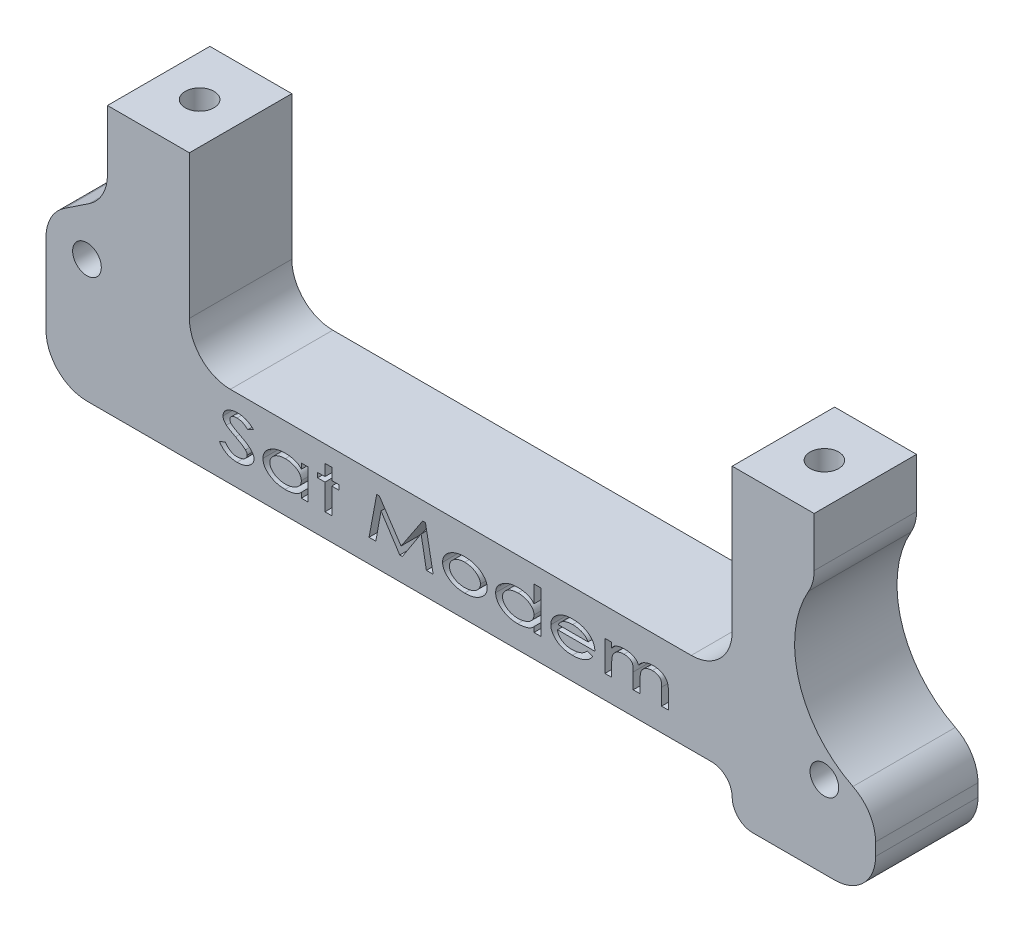
SolidWorks part; units mm, degrees
ref_plane "Front Plane" through (0, 0, 0) normal (0, 0, 1) x (1, 0, 0)
ref_plane "Top Plane" through (0, 0, 0) normal (0, 1, 0) x (1, 0, 0)
ref_plane "Right Plane" through (0, 0, 0) normal (1, 0, 0) x (0, 0, -1)
sketch "Sketch1" plane through (0, 0, 0) normal (0, 0, 1) x (1, 0, 0)
  line L0 (0, 0) -> (-2.54, 0)
  line L1 (0, 0) -> (2.54, 0)
  line L2 (-2.54, 0) -> (-2.54, 6.35)
  line L3 (0, 0) -> (0, 5.08) construction
  line L4 (0, 5.08) -> (0, 13.97) construction
  line L5 (0, 13.97) -> (3.81, 13.97) construction
  line L6 (3.81, 13.97) -> (6.35, 13.97)
  line L7 (3.81, 13.97) -> (1.27, 13.97)
  line L8 (1.27, 13.97) -> (1.27, 8.89)
  line L10 (6.35, 13.97) -> (6.35, 8.89)
  line L11 (2.54, 0) -> (2.54, 6.35)
  line L13 (2.54, 6.35) -> (6.35, 8.89)
  line L14 (-2.54, 6.35) -> (1.27, 8.89)
  circle A0 centre (0, 5.08) radius 0.889
extrude "Boss-Extrude1" add sketch "Sketch1" along normal blind 6.35
ref_plane "Plane1" through (0, 13.97, 0) normal (0, 1, 0) x (1, 0, 0)
sketch "Sketch2" plane through (0, 13.97, 0) normal (0, 1, 0) x (1, 0, 0)
  line L0 (3.81, -6.35) -> (3.81, -3.175) construction
  line L1 (6.35, -6.35) -> (1.27, -6.35) construction
  circle A0 centre (3.81, -3.175) radius 0.889
extrude "Cut-Extrude1" cut sketch "Sketch2" against normal blind 5.08
ref_plane "Plane2" through (0, 0, 6.35) normal (0, 0, 1) x (1, 0, 0)
sketch "Sketch3" plane through (0, 0, 6.35) normal (0, 0, 1) x (1, 0, 0)
  line L1 (2.54, 0) -> (2.54, 6.35) construction
  line L2 (3.81, 13.97) -> (3.81, 5.08) construction
  line L3 (6.35, 13.97) -> (1.27, 13.97) construction
  line L4 (3.81, 5.08) -> (42.545, 5.08) construction
  line L5 (42.545, 5.08) -> (42.545, 13.97) construction
  line L6 (42.545, 13.97) -> (40.005, 13.97)
  line L7 (42.545, 13.97) -> (45.085, 13.97)
  line L8 (45.085, 13.97) -> (45.085, 10.16)
  line L11 (45.085, 10.16) -> (45.085, 6.35) construction
  line L12 (48.895, -5.08) -> (48.895, 0)
  line L13 (42.545, -5.08) -> (45.72, -5.08) construction
  line L14 (45.72, -5.08) -> (45.72, 0) construction
  line L15 (40.005, -5.08) -> (48.895, -5.08)
  line L19 (40.005, 5.08) -> (40.005, 13.97)
  line L20 (2.54, 0) -> (2.54, 5.08)
  line L22 (6.35, 8.89) -> (6.35, 5.08)
  line L23 (2.54, 5.08) -> (2.54, 6.35)
  line L24 (2.54, 6.35) -> (6.35, 8.89)
  line L26 (6.35, 5.08) -> (6.35, 2.54)
  line L27 (6.35, 2.54) -> (6.35, -2.54) construction
  line L28 (6.35, -2.54) -> (-2.54, -2.54)
  line L29 (-2.54, -2.54) -> (-2.54, 0)
  line L30 (-2.54, 0) -> (2.54, 0)
  line L31 (6.35, -2.54) -> (40.005, -2.54)
  line L32 (40.005, -5.08) -> (40.005, -2.54)
  line L33 (6.35, 2.54) -> (40.005, 2.54)
  line L34 (40.005, 2.54) -> (40.005, 5.08)
  arc A1 (45.085, 10.16) -> (48.895, 0) centre (50.4168, 6.365) ccw
  circle A2 centre (45.72, 0) radius 0.889
extrude "Boss-Extrude2" add sketch "Sketch3" against normal blind 6.35 separate body contours A1 L8 L7 L6 L15 L12 A2 region at (26.7958, 1.2796, 6.35)
ref_plane "Plane3" through (0, 13.97, 0) normal (0, 1, 0) x (1, 0, 0)
sketch "Sketch4" plane through (0, 13.97, 0) normal (0, 1, 0) x (1, 0, 0)
  line L0 (3.81, -3.175) -> (42.545, -3.175) construction
  circle A0 centre (42.545, -3.175) radius 0.889
extrude "Cut-Extrude2" cut sketch "Sketch4" against normal blind 5.08
combine bodies "Combine1" operation type add bodies to combine 104 102
fillet "Fillet1" radius 2.54 8 edges at (-2.54, 6.35, 3.175) (1.27, 8.89, 3.175) (45.085, 10.16, 3.175) (48.895, 0, 3.175) (48.895, -5.08, 3.175) (-2.54, -2.54, 3.175) (40.005, 2.54, 3.175) (6.35, 2.54, 3.175)
ref_plane "Plane4" through (0, 0, 6.35) normal (0, 0, 1) x (1, 0, 0)
sketch "Sketch5" plane through (0, 0, 6.35) normal (0, 0, 1) x (1, 0, 0)
  text T0 "<b>Sat Modem</b>" font "Century Gothic" height 2.54
  point P1 (7.38, -0.6071)
  point P2 (0, 0)
  point P3 (7.3654, -1.7039)
  point P4 (7.2008, -0.9165)
  point P5 (0, 0)
  point P6 (7.9361, -1.2325)
  point P7 (8.1443, -1.1056)
extrude "Cut-Extrude3" cut sketch "Sketch5" against normal blind 1.27
fillet "Fillet3" radius 1.27 2 edges at (40.005, -5.08, 3.175) (40.005, -2.54, 3.175)
